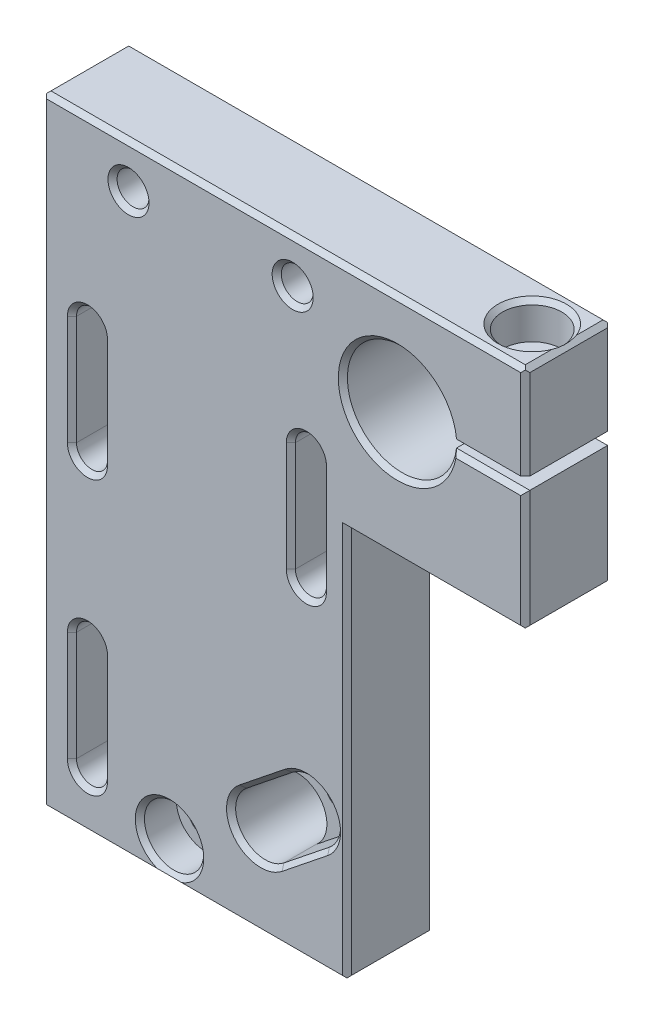
SolidWorks part; units mm, degrees
ref_plane "Front Plane" through (0, 0, 0) normal (0, 0, 1) x (1, 0, 0)
ref_plane "Top Plane" through (0, 0, 0) normal (0, 1, 0) x (1, 0, 0)
ref_plane "Right Plane" through (0, 0, 0) normal (1, 0, 0) x (0, 0, -1)
sketch "Sketch1" plane through (0, 0, 0) normal (0, 0, 1) x (1, 0, 0)
  line L0 (0, 0) -> (24.45, 0)
  line L1 (30, -16) -> (30, 43) construction
  line L3 (24.45, 43) -> (24.45, 0)
  line L4 (24.45, 0) -> (24.6859, 0.0472)
  line L6 (24.45, 43) -> (58.5, 43)
  line L8 (0, 68) -> (58.5, 68)
  line L9 (58.5, 43) -> (58.5, 68)
  line L10 (0, 0) -> (-9, 0)
  line L12 (0, 68) -> (-9, 68)
  line L13 (-9, 0) -> (-9, 68)
  circle A0 centre (5, 4) radius 2
  circle A1 centre (20, 14) radius 2
  circle A2 centre (15, 10) radius 3.25
  circle A3 centre (5, 4) radius 3.25
  circle A4 centre (30, -16) radius 6.55
  circle A5 centre (20, 14) radius 3.25
  dimension "D3" = 4
  dimension "D7" = 4
  dimension "D10" = 6.5
  dimension "D13" = 13.1
  dimension "D19" = 6.5
  dimension "D20" = 6.5
  dimension "D1" = 24.45
  dimension "D2" = 4
  dimension "D4" = 5
  dimension "D5" = 20
  dimension "D6" = 14
  dimension "D8" = 10
  dimension "D9" = 15
  dimension "D11" = 30
  dimension "D12" = 16
  dimension "D14" = 43
  dimension "D15" = 58.5
  dimension "D16" = 67.5
  dimension "D17" = 9
  dimension "D18" = 68
extrude "Boss-Extrude1" add sketch "Sketch1" along normal blind 9.525 contours L13 L10 L0 L3 L6 L9 L8 L12 A2 A1 A0 region at (17.0339, 40.8583, 0)
extrude "Boss-Extrude3" add sketch "Sketch1<4>" along normal blind 5.525 contours A2 A5 A1 | A3 A0 region at (17.6096, 12.0877, 0) region at (1.8419, 4, 0)
sketch "Sketch1<4>" plane through (0, 0, 0) normal (0, 0, 1) x (1, 0, 0) same geometry as "Sketch1"
sketch "Sketch3" plane through (0, 0, 9.525) normal (0, 0, 1) x (1, 0, 0)
  line L0 (-2.3, 18) -> (-2.3, 6)
  line L1 (-9, 0) -> (-9, 68) construction
  line L2 (24.45, 0) -> (-9, 0) construction
  line L3 (-5.7, 18) -> (-5.7, 6)
  line L4 (-5.7, 48) -> (-5.7, 36)
  line L5 (-2.3, 48) -> (-2.3, 36)
  line L6 (18.3, 48) -> (18.3, 36)
  line L7 (21.7, 48) -> (21.7, 36)
  arc A0 (-2.3, 18) -> (-5.7, 18) centre (-4, 18) ccw
  arc A1 (-2.3, 48) -> (-5.7, 48) centre (-4, 48) ccw
  arc A2 (21.7, 48) -> (18.3, 48) centre (20, 48) ccw
  arc A7 (-5.7, 6) -> (-2.3, 6) centre (-4, 6) ccw
  arc A8 (-5.7, 36) -> (-2.3, 36) centre (-4, 36) ccw
  arc A11 (18.3, 36) -> (21.7, 36) centre (20, 36) ccw
  dimension "D3" = 3.4
  dimension "D4" = 3.4
  dimension "D5" = 3.4
  dimension "D6" = 5
  dimension "D7" = 6
  dimension "D8" = 12
  dimension "D11" = 3.4
  dimension "D12" = 3.4
  dimension "D13" = 3.4
  dimension "D1" = 24
  dimension "D2" = 30
  dimension "D9" = 12
  dimension "D10" = 12
  dimension "D14" = 12
  dimension "D15" = 12
  dimension "D16" = 12
  dimension "D17" = 12
  dimension "D18" = 12
  dimension "D19" = 12
extrude "Cut-Extrude1" cut sketch "Sketch3" against normal through all
sketch "Sketch4" plane through (0, 0, 0) normal (0, 0, -1) x (-1, 0, 0)
  line L4 (-16.75, 36) -> (-16.75, 48)
  line L5 (-23.25, 48) -> (-23.25, 36)
  line L8 (0.75, 48) -> (0.75, 36)
  line L9 (7.25, 36) -> (7.25, 48)
  line L12 (7.25, 6) -> (7.25, 18)
  line L13 (0.75, 17.9953) -> (0.75, 5.9953)
  arc A0 (2.3, 6) -> (5.7, 6) centre (4, 6) ccw construction
  arc A1 (5.7, 18) -> (2.3, 18) centre (4, 18) ccw construction
  arc A2 (2.3, 36) -> (5.7, 36) centre (4, 36) ccw construction
  arc A3 (5.7, 48) -> (2.3, 48) centre (4, 48) ccw construction
  arc A4 (-23.25, 36) -> (-16.75, 36) centre (-20, 36) ccw
  arc A5 (-16.75, 48) -> (-23.25, 48) centre (-20, 48) ccw
  arc A6 (-21.7, 36) -> (-18.3, 36) centre (-20, 36) ccw construction
  arc A7 (-18.3, 48) -> (-21.7, 48) centre (-20, 48) ccw construction
  arc A8 (0.75, 36) -> (7.25, 36) centre (4, 36) ccw
  arc A9 (7.25, 48) -> (0.75, 48) centre (4, 48) ccw
  arc A12 (0.75, 5.9953) -> (7.25, 6) centre (4, 6) ccw
  arc A13 (7.25, 18) -> (0.75, 17.9953) centre (4, 18) ccw
  dimension "D4" = 3.25
  dimension "D1" = 3.25
  dimension "D6" = 3.25
  dimension "D7" = 3.25
  dimension "D11" = 3.25
  dimension "D12" = 3.25
  dimension "D2" = 12
  dimension "D3" = 12
  dimension "D5" = 6.5
  dimension "D8" = 12
  dimension "D9" = 12
  dimension "D10" = 6.5
  dimension "D13" = 12
  dimension "D14" = 12
  dimension "D15" = 6.5
extrude "Cut-Extrude2" cut sketch "Sketch4" against normal blind 5.525
chamfer "Chamfer1" distance 0.5 angle 45 1 edges at (-9, 68, 4.7625)
chamfer "Chamfer2" distance 0.5 angle 45 4 edges at (-9, 0, 4.7625) (24.45, 0, 4.7625) (58.5, 43, 4.7625) (58.5, 68, 4.7625)
chamfer "Chamfer3" distance 0.5 angle 45 12 edges at (24.75, 68, 0) (58.5, 55.5, 0) (41.225, 43, 0) (24.45, 21.75, 0) (24.75, 68, 9.525) (58.5, 55.5, 9.525) (41.225, 43, 9.525) (24.45, 21.75, 9.525) (7.725, 0, 0) (7.725, 0, 9.525) (-9, 34, 0) (-9, 34, 9.525)
sketch "Sketch6" plane through (0, 0, 9.525) normal (0, 0, 1) x (1, 0, 0)
  line L0 (0, 68) -> (58.5, 68) construction
  line L1 (22.2, 48) -> (22.2, 36) construction
  line L2 (30, 57.675) -> (50, 57.675)
  line L3 (30, 57.675) -> (30, 56.325)
  line L4 (30, 56.325) -> (50, 56.325)
  line L5 (50, 57.675) -> (50, 56.325)
  line L6 (79, 1) -> (29, 1)
  line L7 (79, 1) -> (79, 51)
  line L8 (79, 51) -> (29, 51)
  line L9 (29, 1) -> (29, 51)
  line L10 (-9, 0) -> (-9, 68) construction
  circle A0 centre (30, 57) radius 6
  dimension "D1" = 12
  dimension "D2" = 73
  dimension "D3" = 1.35
  dimension "D4" = 0.675
  dimension "D5" = 20
  dimension "D6" = 17
  dimension "D7" = 38
  dimension "D8" = 50
  dimension "D9" = 50
sketch "Sketch7" plane through (0, 0, 9.525) normal (0, 0, 1) x (1, 0, 0)
  line L0 (0, 68) -> (58.5, 68) construction
  line L1 (58.5, 43) -> (44, 43)
  line L2 (58.5, 43) -> (58.5, 68)
  line L3 (58.5, 68) -> (44, 68)
  line L4 (44, 43) -> (44, 68)
  dimension "D1" = 14
extrude "Cut-Extrude4" cut sketch "Sketch7" against normal through all
extrude "Cut-Extrude5" cut sketch "Sketch6" against normal through all contours L2 A0 L4 L3 | L4 A0 L2 L3 | A0 L4 L5 L2 region at (29.7696, 57, 9.525) region at (32.9937, 57, 9.525) region at (42.9937, 57, 9.525)
sketch "Sketch9" plane through (0, 0, 9.525) normal (0, 0, 1) x (1, 0, 0)
  line L0 (-8.5, 68) -> (44, 68) construction
  line L1 (-9, 0.5) -> (-9, 67.5) construction
  circle A0 centre (0.5, 63.2375) radius 1.75
  circle A1 centre (18.5, 63.2375) radius 1.75
  circle A2 centre (0.5, 63.2375) radius 3.25
  circle A3 centre (18.5, 63.2375) radius 3.25
  dimension "D1" = 3.5
  dimension "D2" = 3.5
  dimension "D3" = 6.5
  dimension "D6" = 6.5
  dimension "D4" = 4.7625
  dimension "D5" = 4.7625
  dimension "D7" = 9.5
  dimension "D8" = 18
sketch "Sketch10" plane through (0, 0, 0) normal (0, 0, -1) x (-1, 0, 0)
  circle A0 centre (-18.5, 63.2375) radius 1.75 construction
  circle A1 centre (-18.5, 63.2375) radius 3.25 construction
  circle A2 centre (-0.5, 63.2375) radius 1.75 construction
  circle A3 centre (-0.5, 63.2375) radius 3.25 construction
  circle A4 centre (-18.5, 63.2375) radius 1.75
  circle A5 centre (-18.5, 63.2375) radius 3.25
  circle A6 centre (-0.5, 63.2375) radius 1.75
  circle A7 centre (-0.5, 63.2375) radius 3.25
extrude "Cut-Extrude6" cut sketch "Sketch10" against normal blind 4
extrude "Cut-Extrude7" cut sketch "Sketch9" against normal through all contours A0 | A1 region at (0.5, 63.2375, 9.525) region at (18.5, 63.2375, 9.525)
chamfer "Chamfer5" distance 0.5 angle 45 2 edges at (-2.75, 63.2375, 0) (15.25, 63.2375, 0)
sketch "Sketch12" plane through (0, 68, 0) normal (0, 1, 0) x (1, 0, 0)
  line L0 (44, -0.5) -> (44, -9.025) construction
  line L1 (-8.5, 0) -> (44, 0) construction
  circle A0 centre (40, -4.7625) radius 1.75
  circle A1 centre (40, -4.7625) radius 3.25
  dimension "D3" = 3.5
  dimension "D4" = 6.5
  dimension "D1" = 4
  dimension "D2" = 4.7625
extrude "Cut-Extrude8" cut sketch "Sketch12" against normal up to surface (10.325 mm away) contours A0 region at (40, 68, 4.7625) up to face at (39.981, 57.675, 4.7625)
sketch "Sketch13" plane through (0, 43, 0) normal (0, -1, 0) x (1, 0, 0)
  line L0 (44, 0) -> (23.95, 0) construction
  line L1 (44, 0.5) -> (44, 9.025) construction
  circle A0 centre (40, 4.7625) radius 1.2195
  dimension "D1" = 2.439
  dimension "D2" = 4.7625
  dimension "D3" = 4
extrude "Cut-Extrude9" cut sketch "Sketch13" against normal up to surface (13.325 mm away) up to face at (39.981, 56.325, 4.7625)
extrude "Cut-Extrude10" cut sketch "Sketch12<3>" against normal blind 4
sketch "Sketch12<3>" plane through (0, 68, 0) normal (0, 1, 0) x (1, 0, 0) same geometry as "Sketch12"
chamfer "Chamfer6" distance 0.5 angle 45 1 edges at (36.75, 68, 4.7625)
chamfer "Chamfer7" distance 0.5 angle 45 26 edges at (7, 4, 0) (22, 14, 0) (18.25, 10, 0) (-3.9977, 21.25, 0) (-7.25, 12, 0) (-4.0023, 2.75, 0) (-0.75, 11.9953, 0) (20, 32.75, 0) (23.25, 42, 0) (20, 51.25, 0) (16.75, 42, 0) (-4, 51.25, 0) (-7.25, 42, 0) (-4, 32.75, 0) (-0.75, 42, 0) (44, 68, 4.7625) (44, 62.5875, 0) (44, 62.5875, 9.525) (39.981, 57.675, 0) (24, 57, 0) (39.981, 56.325, 0) (24, 57, 9.525) (39.981, 56.325, 9.525) (44, 49.9125, 0) (44, 49.9125, 9.525) (44, 43, 4.7625)
sketch "Sketch16" plane through (0, 0, 9.525) normal (0, 0, 1) x (1, 0, 0)
  line L0 (12.9697, 12.5378) -> (17.9697, 16.5378)
  line L1 (17.0303, 7.4622) -> (22.0303, 11.4622)
  arc A0 (17.1508, 12.4365) -> (17.8492, 11.5635) centre (15, 10) ccw construction
  arc A1 (17.8492, 11.5635) -> (17.1508, 12.4365) centre (20, 14) ccw construction
  circle A2 centre (15, 10) radius 3.25
  circle A3 centre (20, 14) radius 3.25
  arc M4 (17.1508, 12.4365) -> (17.8492, 11.5635) centre (20, 14) cw
  arc M5 (17.8492, 11.5635) -> (17.1508, 12.4365) centre (15, 10) cw
  dimension "D1" = 6.5
extrude "Cut-Extrude11" cut sketch "Sketch16" against normal up to surface (4 mm away) contours L0 M5 M4 | L1 M5 M4 region at (15.894, 14.0075, 9.525) region at (19.106, 9.9925, 9.525) up to face at (22, 14, 5.525)
chamfer "Chamfer9" distance 0.5 angle 45 17 edges at (8.25, 4, 9.525) (22.5378, 16.0303, 9.525) (19.5303, 9.4622, 9.525) (12.4622, 7.9697, 9.525) (15.4697, 14.5378, 9.525) (20, 49.7, 9.525) (21.7, 42, 9.525) (20, 34.3, 9.525) (18.3, 42, 9.525) (-2.3, 42, 9.525) (-4, 49.7, 9.525) (-4, 34.3, 9.525) (-5.7, 42, 9.525) (-4, 19.7, 9.525) (-5.7, 12, 9.525) (-4, 4.3, 9.525) (-2.3, 12, 9.525)
chamfer "Chamfer10" distance 0.5 angle 45 3 edges at (40, 43, 3.543) (20.25, 63.2375, 9.525) (2.25, 63.2375, 9.525)
